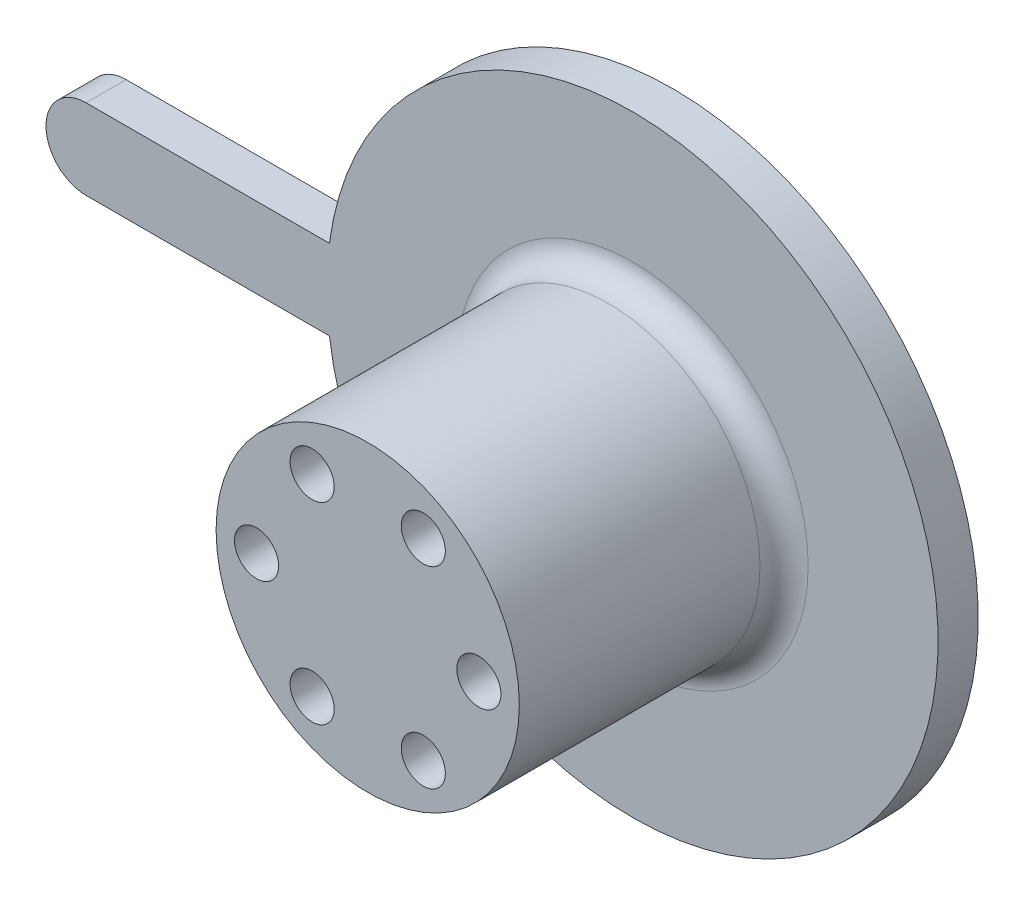
SolidWorks part; units mm, degrees
ref_plane "Front Plane" through (0, 0, 0) normal (0, 0, 1) x (1, 0, 0)
ref_plane "Top Plane" through (0, 0, 0) normal (0, 1, 0) x (1, 0, 0)
ref_plane "Right Plane" through (0, 0, 0) normal (1, 0, 0) x (0, 0, -1)
sketch "Sketch4" plane through (0, 0, 0) normal (0, 0, 1) x (1, 0, 0)
  line L0 (-38.1, 0) -> (-68.1, 0)
  line L1 (-68.1, 0) -> (-68.1, 5)
  line L2 (-68.1, 0) -> (-68.1, -5)
  line L3 (-68.1, 5) -> (-37.7705, 5)
  line L4 (-68.1, -5) -> (-37.7705, -5)
  circle A0 centre (0, 0) radius 38.1
  arc A1 (-68.1, 5) -> (-68.1, -5) centre (-68.1, 0) ccw
  dimension "D1" = 30
  dimension "D2" = 76.2
extrude "Boss-Extrude3" add sketch "Sketch4" along normal blind 5 contours A0 | A0 L3 L1 L0 | A0 L0 L2 L4 | L1 A1 L2 region at (-53.045, -2.5046, 0) region at (-53.045, 2.5046, 0) region at (0, 0, 0) region at (-70.2221, 0, 0)
sketch "Sketch5" plane through (0, 0, 5) normal (0, 0, 1) x (1, 0, 0)
  circle A0 centre (0, 0) radius 18.9
extrude "Boss-Extrude4" add sketch "Sketch5" along normal blind 33
fillet "Fillet4" radius 3 1 edges at (18.9, 0, 5)
sketch "Sketch6" plane through (0, 0, 38) normal (0, 0, 1) x (1, 0, 0)
  line L7 (-13.8564, 0) -> (-6.9282, -12)
  line L8 (-6.9282, -12) -> (6.9282, -12)
  line L9 (6.9282, -12) -> (13.8564, 0)
  line L10 (13.8564, 0) -> (6.9282, 12)
  line L11 (6.9282, 12) -> (-6.9282, 12)
  line L12 (-6.9282, 12) -> (-13.8564, 0)
  circle A0 centre (0, 0) radius 12 construction
  circle A7 centre (-13.8564, 0) radius 2.75
  circle A8 centre (-6.9282, 12) radius 2.75
  circle A9 centre (6.9282, 12) radius 2.75
  circle A10 centre (13.8564, 0) radius 2.75
  circle A11 centre (6.9282, -12) radius 2.75
  circle A12 centre (-6.9282, -12) radius 2.75
extrude "Cut-Extrude4" cut sketch "Sketch6" against normal blind 39.48 contours L12 A7 L7 | L7 A7 L12 | L11 A8 L12 | L12 A8 L11 | L10 A9 L11 | L11 A9 L10 | L7 A12 L8 | L8 A12 L7 | L9 A11 L8 | L8 A11 L9 | L9 A10 L10 | L10 A10 L9 region at (-12.3403, 0, 38) region at (-14.6145, 0, 38) region at (-6.1701, -10.687, 38) region at (-7.3072, -12.6565, 38) region at (-7.3072, 12.6565, 38) region at (-6.1701, 10.687, 38) region at (6.1701, -10.687, 38) region at (7.3072, -12.6565, 38) region at (7.3072, 12.6565, 38) region at (6.1701, 10.687, 38) region at (12.3403, 0, 38) region at (14.6145, 0, 38)
